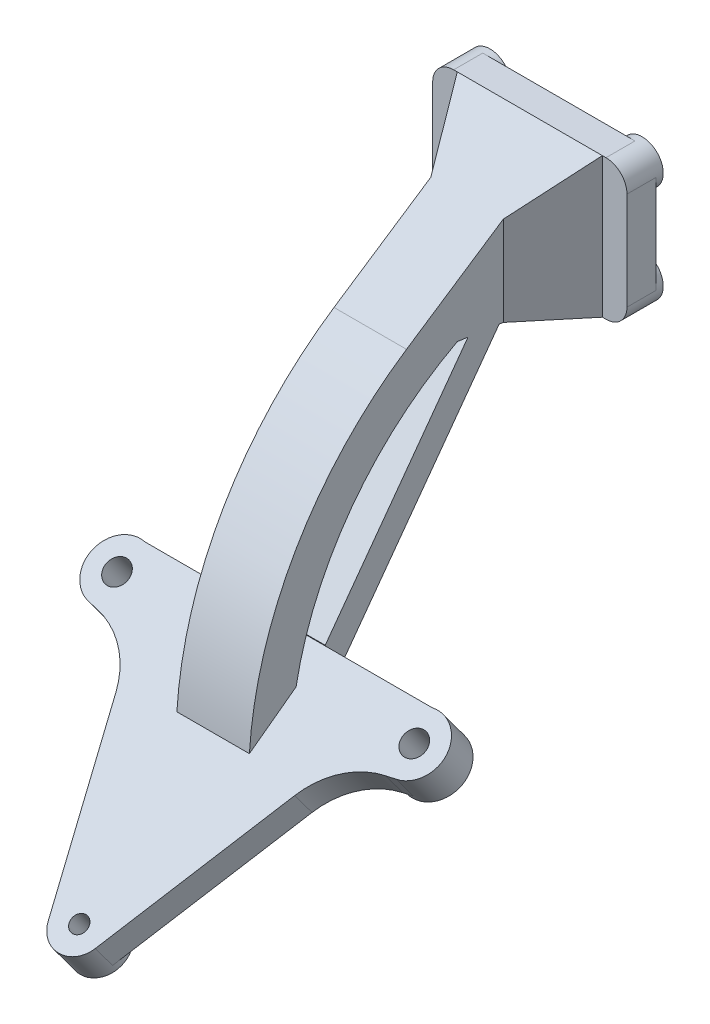
SolidWorks part; units mm, degrees
ref_plane "Ebene vorne" through (0, 0, 0) normal (0, 0, 1) x (1, 0, 0)
ref_plane "Ebene oben" through (0, 0, 0) normal (0, 1, 0) x (1, 0, 0)
ref_plane "Ebene rechts" through (0, 0, 0) normal (1, 0, 0) x (0, 0, -1)
sketch "Skizze1" plane through (0, 0, 0) normal (0, 0, 1) x (1, 0, 0)
  line L0 (0, 12) -> (0, 3.25) construction
  line L1 (-8.2, 12) -> (8.2, 12) construction
  line L2 (0, 3.25) -> (12.5014, 3.25) construction
  circle A0 centre (-10.5, 10) radius 2.9
  circle A1 centre (10.5, 10) radius 2.9
  circle A2 centre (10.5, -3.5) radius 2.9
  circle A3 centre (-10.5, -3.5) radius 2.9
  dimension "D1" = 5.8
extrude "Aufsatz-Linear austragen1" add sketch "Skizze1" along normal blind 5
sketch "Skizze2" plane through (0, -6.1361, -4.5289) normal (0, 0.8046, 0.5938) x (1, 0, 0)
  line L0 (0, -80.3863) -> (0, -90.3863) construction
  line L1 (0, -90.3863) -> (18.025, -104.5833) construction
  circle A0 centre (20.5, -53.441) radius 4
  arc A1 (24.5, -53.441) -> (18.025, -50.2986) centre (20.5, -53.441) ccw construction
  circle A2 centre (-20.5, -53.441) radius 4
  arc A3 (-18.025, -50.2986) -> (-24.5, -53.441) centre (-20.5, -53.441) ccw construction
  circle A6 centre (0, -85.3863) radius 3.5
  dimension "D1" = 7
extrude "Aufsatz-Linear austragen2" add sketch "Skizze2" along normal blind 5 separate body
sketch "Skizze3" plane through (0, -2.1132, -1.5597) normal (0, 0.8046, 0.5938) x (1, 0, 0)
  line L0 (3.2536, -86.6762) -> (12.3339, -63.7717)
  line L1 (19.8983, -57.6081) -> (21.1927, -57.3805)
  line L2 (13.1898, -60.0569) -> (24.8999, -57.9979) construction
  line L3 (12.3503, -70.5139) -> (19.3014, -52.9803) construction
  line L4 (0, -80.3863) -> (0, -49.5014) construction
  line L5 (21.1927, -57.3805) -> (19.8073, -49.5014)
  line L6 (19.8073, -49.5014) -> (-19.8073, -49.5014)
  line L7 (-12.3503, -70.5139) -> (-19.3014, -52.9803) construction
  line L8 (-13.1898, -60.0569) -> (-24.8999, -57.9979) construction
  line L9 (-21.1927, -57.3805) -> (-19.8073, -49.5014)
  line L10 (-19.8983, -57.6081) -> (-21.1927, -57.3805)
  line L11 (-3.2536, -86.6762) -> (-12.3339, -63.7717)
  line L12 (3.2536, -86.6762) -> (-3.2536, -86.6762)
  circle A0 centre (0, -85.3863) radius 3.5 construction
  circle A1 centre (20.5, -53.441) radius 4 construction
  circle A2 centre (20, -63.4285) radius 4.5 construction
  arc A3 (12.3339, -63.7717) -> (19.8983, -57.6081) centre (21.6301, -67.457) cw
  arc A4 (-12.3339, -63.7717) -> (-19.8983, -57.6081) centre (-21.6301, -67.457) ccw
  dimension "D3" = 10
  dimension "D1" = 2.5
  dimension "D2" = 5
extrude "Aufsatz-Linear austragen3" add sketch "Skizze3" against normal blind 4
sketch "Skizze4" plane through (0, 0, 0) normal (1, 0, 0) x (0, 0, -1)
  line L0 (-48.6793, -39.1931) -> (-42.2426, -34.4424)
  line L1 (-68.1785, -53.585) -> (-49.7499, -39.9834) construction
  line L2 (-5, 12.9) -> (-5, 7.1) construction
  line L3 (0, 7.1) -> (0, -0.6) construction
  line L4 (-5, 7.1) -> (0, 7.1) construction
  line L5 (0, -0.6) -> (-5, -0.6) construction
  line L6 (-5, 6.1697) -> (-5, 0.3303)
  line L7 (-5, 3.25) -> (0, 3.25) construction
  line L8 (0, 7.1) -> (0, 12.9) construction
  line L9 (-5, -0.6) -> (-5, -6.4) construction
  line L10 (-35.2505, -35.4961) -> (-38.2197, -31.4732) construction
  arc A0 (-42.2426, -34.4424) -> (-5, 0.3303) centre (0, -42.3552) cw
  arc A1 (-48.6793, -39.1931) -> (-5, 6.1697) centre (0, -42.3552) cw
  dimension "D1" = 8
  dimension "D2" = 5
extrude "Aufsatz-Linear austragen4" add sketch "Skizze4" along normal mid plane 10
sketch "Skizze5" plane through (0, 0, 5) normal (0, 0, 1) x (1, 0, 0)
  line L13 (-13.4, 12.9) -> (13.4, 12.9)
  line L14 (-13.4, 12.9) -> (-13.4, -6.4)
  line L15 (-13.4, -6.4) -> (13.4, -6.4)
  line L16 (13.4, 12.9) -> (13.4, -6.4)
  circle A4 centre (10.5, -3.5) radius 2.9 construction
  circle A5 centre (10.5, 10) radius 2.9 construction
  circle A6 centre (-10.5, 10) radius 2.9 construction
  circle A7 centre (-10.5, -3.5) radius 2.9 construction
extrude "Aufsatz-Linear austragen5" add sketch "Skizze5" against normal blind 4
sketch "Skizze6" plane through (0, 0, 0) normal (0, 0, -1) x (-1, 0, 0)
  line L0 (-13.4, 10) -> (-13.4, 12.9)
  line L1 (-13.4, 12.9) -> (-10.5, 12.9)
  line L2 (0, 11.9883) -> (0, 3.25) construction
  line L3 (0, 3.25) -> (16.6468, 3.25) construction
  line L4 (13.4, 12.9) -> (10.5, 12.9)
  line L5 (13.4, 10) -> (13.4, 12.9)
  line L6 (13.4, -3.5) -> (13.4, -6.4)
  line L7 (13.4, -6.4) -> (10.5, -6.4)
  line L8 (-13.4, -6.4) -> (-10.5, -6.4)
  line L9 (-13.4, -3.5) -> (-13.4, -6.4)
  arc A0 (-13.4, 10) -> (-10.5, 12.9) centre (-10.5, 10) cw
  circle A1 centre (-10.5, 10) radius 2.9 construction
  arc A2 (13.4, 10) -> (10.5, 12.9) centre (10.5, 10) ccw
  arc A3 (13.4, -3.5) -> (10.5, -6.4) centre (10.5, -3.5) cw
  arc A4 (-13.4, -3.5) -> (-10.5, -6.4) centre (-10.5, -3.5) ccw
  arc A5 (10.5, -6.4) -> (13.4, -3.5) centre (10.5, -3.5) ccw construction
extrude "Schnitt-Linear austragen1" cut sketch "Skizze6" against normal up to next
sketch "Skizze7" plane through (-5, 0, 0) normal (-1, 0, 0) x (0, 0, 1)
  line L7 (11.1141, -0.8398) -> (35.8443, -34.6916)
  line L9 (38.2197, -31.4732) -> (35.2505, -35.4961) construction
  line L10 (35.8443, -34.6916) -> (38.2197, -31.4732)
  line L11 (38.2197, -31.4732) -> (17.4902, -3.0978)
  line L12 (35.8443, -34.6916) -> (51.7572, -46.4364) construction
  line L13 (47.3746, -43.2017) -> (65.8031, -56.8033) construction
  arc A0 (42.2426, -34.4424) -> (5, 0.3303) centre (0, -42.3552) ccw construction
  arc A6 (11.1141, -0.8398) -> (17.4902, -3.0978) centre (0, -42.3552) cw
  dimension "D1" = 40
extrude "Aufsatz-Linear austragen6" add sketch "Skizze7" against normal up to surface (10 mm away) up to face at (5, -13.2573, 28.7327)
sketch "Skizze9" plane through (-13.4, 0, 0) normal (-1, 0, 0) x (0, 0, 1)
  line L0 (5, 12.9) -> (27.0083, -1.7323)
  line L2 (5, 10) -> (5, -3.5) construction
  line L3 (5, 6.1697) -> (5, 12.9)
  line L4 (5, -6.4) -> (20, -4.3151)
  line L6 (5, 0.3303) -> (5, -6.4)
  arc A0 (48.6793, -39.1931) -> (5, 6.1697) centre (0, -42.3552) ccw construction
  arc A1 (5, 6.1697) -> (27.0083, -1.7323) centre (0, -42.3552) cw
  arc A2 (5, 0.3303) -> (20, -4.3151) centre (0, -42.3552) cw
  arc A3 (11.1141, -0.8398) -> (5, 0.3303) centre (0, -42.3552) ccw construction
  dimension "D1" = 15
extrude "Aufsatz-Linear austragen8" add sketch "Skizze9" against normal up to surface (10 mm away) from surface up to face at (5, -15.7606, 26.9717) starting at face at (-5, -15.7606, 26.9717)
chamfer "Fase6" distance 5 angle 60 1 edges at (-5, 3.25, 5) first distance on face at (-9.8335, 3.25, 5)
chamfer "Fase7" distance 5 angle 60 1 edges at (5, 3.25, 5) first distance on face at (9.8335, 3.25, 5)
sketch "Skizze10" plane through (0, -2.1132, -1.5597) normal (0, 0.8046, 0.5938) x (1, 0, 0)
  circle A0 centre (-20.5, -53.441) radius 1.65
  circle A3 centre (20.5, -53.441) radius 1.65
  circle A4 centre (20.5, -53.441) radius 1.65 construction
  circle A5 centre (-20.5, -53.441) radius 1.65 construction
  circle A6 centre (0, -85.3863) radius 1.15
  arc A7 (3.2536, -86.6762) -> (-3.2536, -86.6762) centre (0, -85.3863) ccw construction
  dimension "D1" = 2.3
extrude "Schnitt-Linear austragen2" cut sketch "Skizze10" against normal through all
sketch "Skizze11" plane through (0, 0, 0) normal (0, 0, -1) x (-1, 0, 0)
  line L0 (0, 10.4616) -> (0, 3.25) construction
  line L1 (0, 3.25) -> (16.0289, 3.25) construction
  circle A0 centre (-10.5, -3.5) radius 1.7
  circle A1 centre (10.5, -3.5) radius 1.7
  circle A2 centre (10.5, 10) radius 1.7
  circle A3 centre (-10.5, 10) radius 1.7
  dimension "D1" = 3.4
extrude "Schnitt-Linear austragen3" cut sketch "Skizze11" against normal blind 4
equation "\"M2EinschmelzGewindeDurchmesser\"=3.4"
equation "\"M2EinschmelzGewindeTiefe\"= 4.0"
equation "\"M3EinschmelzGewindeDurchmesser\"= 4.2"
equation "\"M3EinschmelzGewindeTief\"= 5.7"
equation "\"M2SchraubeLoch\"=2.3"
equation "\"M3SchraubeLoch\"=3.3"
equation "\"offSetVonGummiReifen\"= 3.0"
equation "\"D1@Skizze10\"=\"M2SchraubeLoch\""
equation "\"D1@Skizze11\"=\"M2EinschmelzGewindeDurchmesser\""
equation "\"D1@Schnitt-Linear austragen3\"=\"M2EinschmelzGewindeTiefe\""
